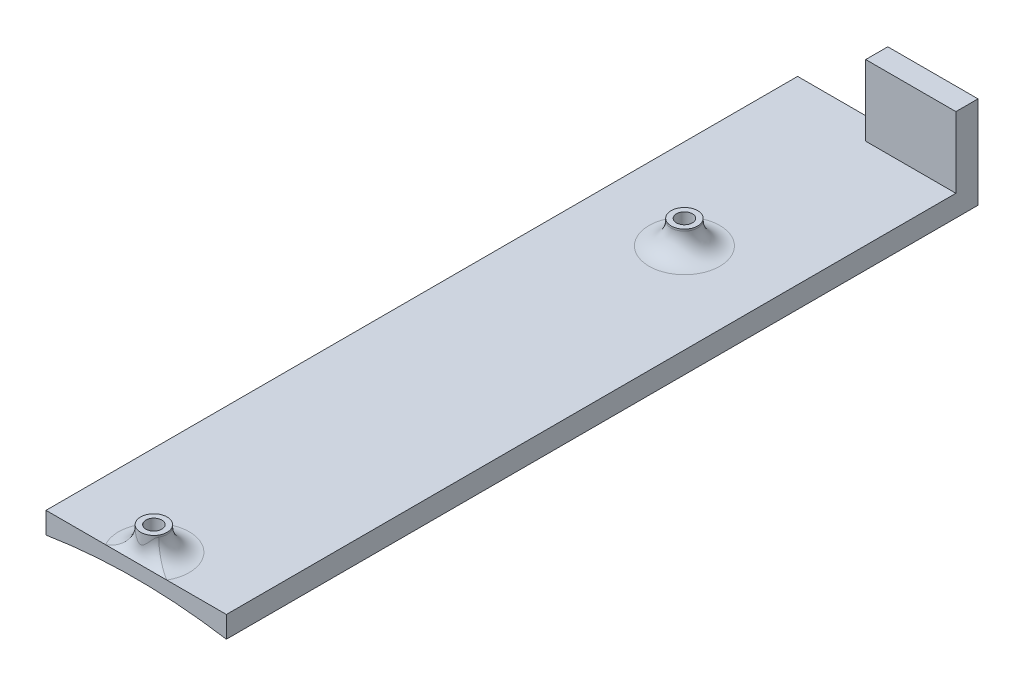
SolidWorks part; units mm, degrees
ref_plane "Front Plane" through (0, 0, 0) normal (0, 0, 1) x (1, 0, 0)
ref_plane "Top Plane" through (0, 0, 0) normal (0, 1, 0) x (1, 0, 0)
ref_plane "Right Plane" through (0, 0, 0) normal (1, 0, 0) x (0, 0, -1)
sketch "Sketch3" plane through (0, 0, 0) normal (0, 0, 1) x (1, 0, 0)
  line L0 (-12.954, -3.81) -> (12.954, -3.81)
  line L3 (-12.954, -6.8909) -> (-12.954, -3.81)
  line L4 (12.954, -6.8909) -> (12.954, -3.81)
  line L5 (0, -3.81) -> (0, -5.842) construction
  arc A2 (12.954, -6.8909) -> (-12.954, -6.8909) centre (0, -86.36) ccw
  circle A3 centre (0, 0) radius 15.24 construction
  dimension "D1" = 2.032
  dimension "D2" = 25.908
  dimension "D3" = 161.036
  dimension "D4" = 30.48
  dimension "D5" = 3.81
extrude "Boss-Extrude1" add sketch "Sketch3" along normal blind 107.95
sketch "Sketch4" plane through (0, -3.81, 0) normal (0, 1, 0) x (1, 0, 0)
  line L1 (12.954, -107.95) -> (-12.954, -107.95) construction
  circle A0 centre (0, -29.21) radius 1.143
  circle A1 centre (0, -105.41) radius 1.143
  circle A2 centre (0, -29.21) radius 1.905
  circle A3 centre (0, -105.41) radius 1.905
  dimension "D1" = 76.2
  dimension "D2" = 2.286
  dimension "D3" = 2.54
  dimension "D4" = 3.81
  dimension "D5" = 3.81
extrude "Boss-Extrude2" add sketch "Sketch4" along normal blind 3.429
fillet "Fillet1" radius 3.175 2 edges at (1.905, -3.81, 29.21) (1.905, -3.81, 105.41)
sketch "Sketch5" plane through (0, -3.81, 0) normal (0, 1, 0) x (1, 0, 0)
  line L0 (12.954, -107.95) -> (12.954, 0) construction
  line L1 (-12.954, 0) -> (12.954, 0)
  line L2 (-12.954, 0) -> (-12.954, -3.175)
  line L3 (-12.954, -3.175) -> (12.954, -3.175)
  line L4 (12.954, 0) -> (12.954, -3.175)
  dimension "D1" = 3.175
extrude "Boss-Extrude3" add sketch "Sketch5" along normal blind 10.16
sketch "Sketch8" plane through (0, 0, 0) normal (0, 0, -1) x (-1, 0, 0)
  line L5 (0, 6.35) -> (0, -5.842)
  line L12 (12.954, -6.8909) -> (12.954, 6.35)
  line L13 (12.954, 6.35) -> (-12.954, 6.35)
  line L14 (-12.954, 6.35) -> (-12.954, -6.8909)
  line L15 (12.954, -6.8909) -> (12.954, 6.35)
  line L16 (12.954, 6.35) -> (-12.954, 6.35)
  line L17 (-12.954, 6.35) -> (-12.954, -6.8909)
  arc A1 (12.954, -6.8909) -> (-12.954, -6.8909) centre (0, -86.36) ccw
  arc A2 (12.954, -6.8909) -> (-12.954, -6.8909) centre (0, -86.36) ccw
  point P0 (0, 0)
  line M5 (12.954, -6.8909) -> (12.954, 6.35)
  line M6 (12.954, 6.35) -> (-12.954, 6.35)
  arc M8 (-12.954, -6.8909) -> (12.954, -6.8909) centre (0, -86.36) cw
  dimension "D1" = 0
extrude "Cut-Extrude1" cut sketch "Sketch8" against normal up to surface (3.175 mm away) contours L5 M6 M8 M5 region at (-6.5672, 0.0758, 0) up to face at (0, 1.27, 3.175)
sketch "Sketch9" plane through (0, 0, 3.175) normal (0, 0, -1) x (-1, 0, 0)
  line L3 (12.954, -3.81) -> (0, -3.81)
  line L4 (0, -3.81) -> (0, -5.842)
  line L5 (0, -3.81) -> (0, -5.842)
  line L6 (12.954, -3.81) -> (0, -3.81)
  line L9 (12.954, -6.8909) -> (12.954, -3.81)
  line L10 (12.954, -6.8909) -> (12.954, -3.81)
  arc A1 (12.954, -6.8909) -> (0, -5.842) centre (0, -86.36) ccw
  arc A2 (12.954, -6.8909) -> (0, -5.842) centre (0, -86.36) ccw
  dimension "D1" = 0
extrude "Boss-Extrude4" add sketch "Sketch9" along normal blind 3.175
